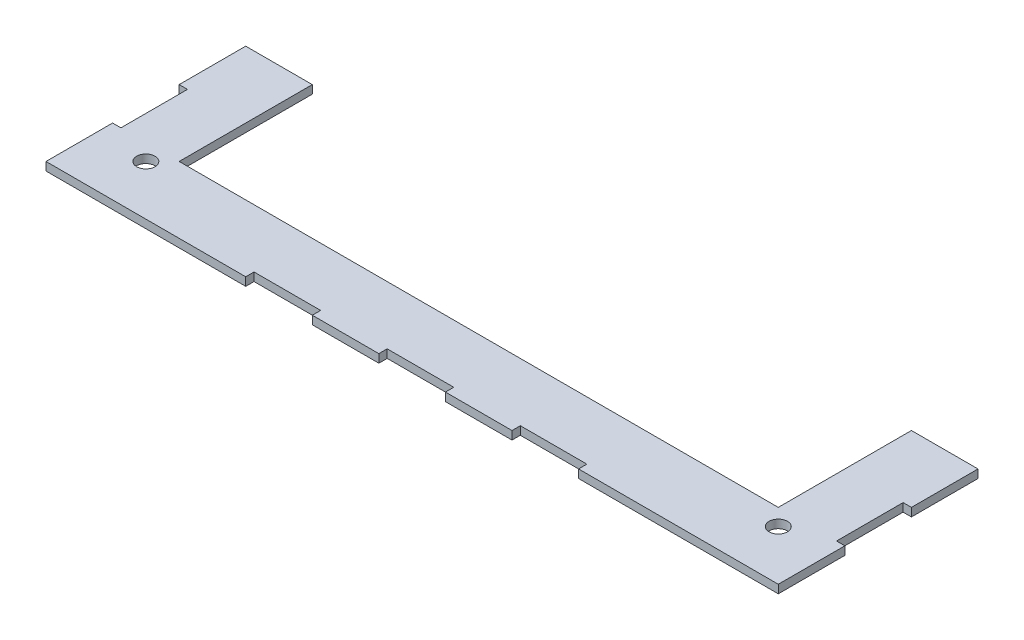
SolidWorks part; units mm, degrees
ref_plane "Front Plane" through (0, 0, 0) normal (0, 0, 1) x (1, 0, 0)
ref_plane "Top Plane" through (0, 0, 0) normal (0, 1, 0) x (1, 0, 0)
ref_plane "Right Plane" through (0, 0, 0) normal (1, 0, 0) x (0, 0, -1)
sketch "Sketch1" plane through (0, 0, 0) normal (0, 1, 0) x (1, 0, 0)
  line L0 (-139.7, 63.5) -> (-114.3, 63.5)
  line L1 (-114.3, 63.5) -> (-114.3, 12.7)
  line L2 (-114.3, 12.7) -> (114.3, 12.7)
  line L3 (114.3, 12.7) -> (114.3, 63.5)
  line L4 (114.3, 63.5) -> (139.7, 63.5)
  line L5 (139.7, 63.5) -> (139.7, -12.7)
  line L6 (139.7, -12.7) -> (-139.7, -12.7)
  line L7 (-139.7, -12.7) -> (-139.7, 63.5)
  line L8 (0, 12.7) -> (0, -12.7) construction
  line L9 (-114.3, 12.7) -> (-114.3, 6.35) construction
  line L10 (-114.3, 6.35) -> (-120.65, 6.35) construction
  line L11 (114.3, 12.7) -> (114.3, 6.35) construction
  line L12 (114.3, 6.35) -> (120.65, 6.35) construction
  line L13 (-38.1, -9.525) -> (-12.7, -9.525) construction
  line L14 (-12.7, -12.7) -> (12.7, -12.7)
  line L15 (-12.7, -12.7) -> (-12.7, -9.525)
  line L16 (-12.7, -9.525) -> (12.7, -9.525)
  line L17 (12.7, -12.7) -> (12.7, -9.525)
  line L18 (38.1, -12.7) -> (63.5, -12.7)
  line L19 (38.1, -12.7) -> (38.1, -9.525)
  line L20 (38.1, -9.525) -> (63.5, -9.525)
  line L21 (63.5, -12.7) -> (63.5, -9.525)
  line L22 (-63.5, -12.7) -> (-38.1, -12.7)
  line L23 (-63.5, -12.7) -> (-63.5, -9.525)
  line L24 (-63.5, -9.525) -> (-38.1, -9.525)
  line L25 (-38.1, -12.7) -> (-38.1, -9.525)
  line L26 (12.7, -9.525) -> (38.1, -9.525) construction
  line L27 (-136.525, 12.7) -> (-136.525, -12.7) construction
  line L28 (-139.7, 12.7) -> (-136.525, 12.7)
  line L29 (-139.7, 12.7) -> (-139.7, 38.1)
  line L30 (-139.7, 38.1) -> (-136.525, 38.1)
  line L31 (-136.525, 12.7) -> (-136.525, 38.1)
  line L32 (139.7, 12.7) -> (136.525, 12.7)
  line L33 (139.7, 12.7) -> (139.7, 38.1)
  line L34 (139.7, 38.1) -> (136.525, 38.1)
  line L35 (136.525, 12.7) -> (136.525, 38.1)
  circle A0 centre (-120.65, 6.35) radius 3.5
  circle A1 centre (120.65, 6.35) radius 3.5
  point P10 (0, 12.7)
  point P11 (0, -12.7)
  point P14 (0, 0)
  point P32 (0, -9.525)
  dimension "D5" = 7
  dimension "D1" = 279.4
  dimension "D2" = 76.2
  dimension "D3" = 25.4
  dimension "D4" = 25.4
  dimension "D6" = 6.35
  dimension "D7" = 25.4
  dimension "D8" = 3.175
  dimension "D9" = 25.4
  dimension "D10" = 3.175
extrude "Boss-Extrude1" add sketch "Sketch1" along normal blind 3.175 contours L25 L6 L15 L16 L17 L19 L20 L21 L5 L4 L3 L2 L1 L0 L7 L23 L24 A1 A0 region at (0, 0, -10.4842)
